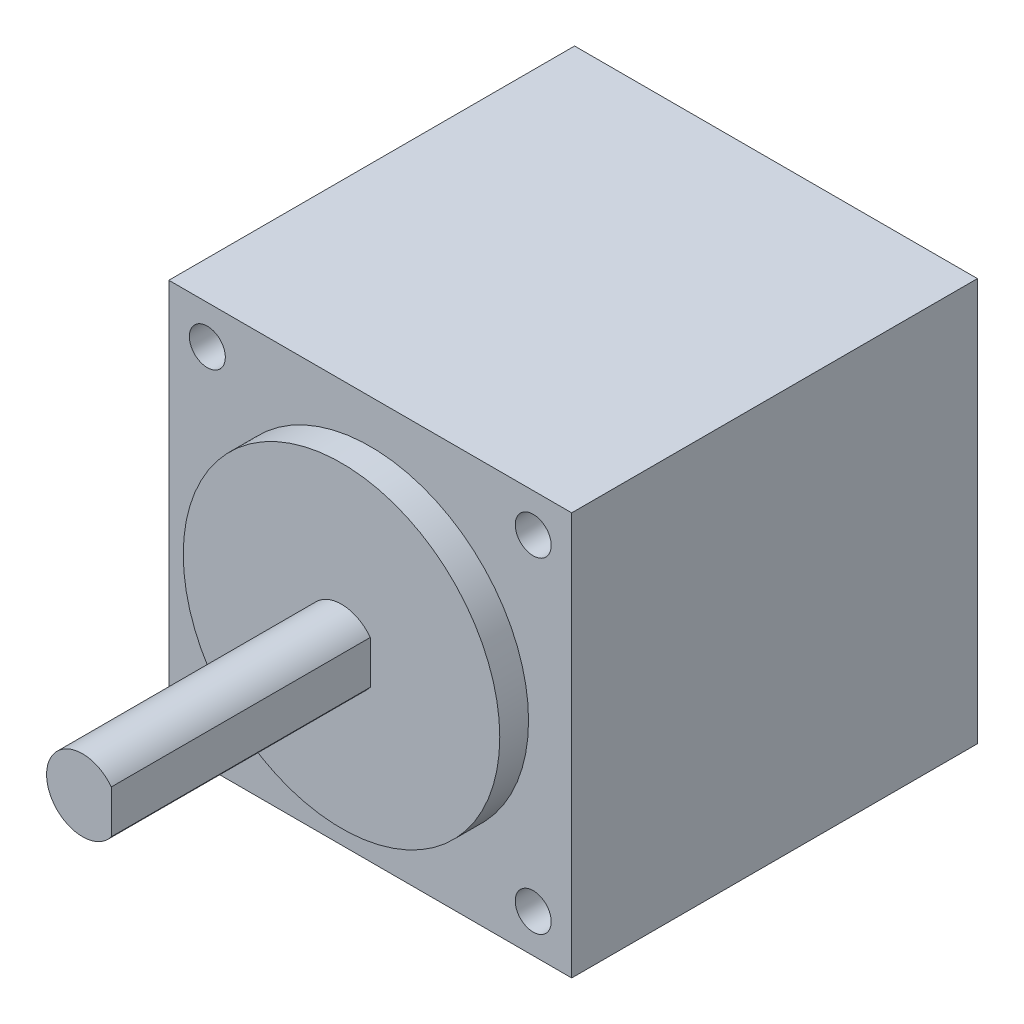
SolidWorks part; units mm, degrees
material "Plain Carbon Steel"
ref_plane "Front Plane" through (0, 0, 0) normal (0, 0, 1) x (1, 0, 0)
ref_plane "Top Plane" through (0, 0, 0) normal (0, 1, 0) x (1, 0, 0)
ref_plane "Right Plane" through (0, 0, 0) normal (1, 0, 0) x (0, 0, -1)
sketch "Sketch2" plane through (0, 0, 0) normal (0, 0, 1) x (1, 0, 0)
  line L1 (-14, -14) -> (14, -14)
  line L2 (-14, -14) -> (-14, 14)
  line L3 (-14, 14) -> (14, 14)
  line L4 (14, -14) -> (14, 14)
  line L5 (-14, -14) -> (14, 14) construction
  line L6 (-14, 14) -> (14, -14) construction
  point P0 (0, 0)
  dimension "D1" = 28
  dimension "D2" = 28
extrude "Boss-Extrude1" add sketch "Sketch2" against normal blind 28.2
sketch "Sketch3" plane through (0, 0, 0) normal (0, 0, 1) x (1, 0, 0)
  circle A0 centre (0, 0) radius 11
  dimension "D1" = 22
extrude "Boss-Extrude2" add sketch "Sketch3" along normal blind 2
sketch "Sketch4" plane through (0, 0, 0) normal (0, 0, 1) x (1, 0, 0)
  circle A0 centre (0, 0) radius 2.5
extrude "Boss-Extrude3" add sketch "Sketch4" along normal blind 20
sketch "Sketch5" plane through (0, 0, 20) normal (0, 0, 1) x (1, 0, 0)
  line L0 (2, 1.5) -> (2, -1.5)
  circle A0 centre (0, 0) radius 2.5 construction
  circle A1 centre (0, 0) radius 2.5
  point P5 (-2.5, 0)
  circle M2 centre (0, 0) radius 2.5
  dimension "D1" = 4.5
extrude "Cut-Extrude1" cut sketch "Sketch5" against normal up to surface (18 mm away) contours L0 M2 region at (2.2018, 0, 20) up to face at (2.5, 0, 2)
sketch "Sketch6" plane through (0, 0, 0) normal (0, 0, 1) x (1, 0, 0)
  line L1 (-11.325, -11.325) -> (11.325, -11.325)
  line L2 (-11.325, -11.325) -> (-11.325, 11.325)
  line L3 (-11.325, 11.325) -> (11.325, 11.325)
  line L4 (11.325, -11.325) -> (11.325, 11.325)
  line L5 (-11.325, -11.325) -> (11.325, 11.325) construction
  line L6 (-11.325, 11.325) -> (11.325, -11.325) construction
  point P0 (0, 0)
  point P7 (-11.325, 11.325)
  point P8 (11.325, 11.325)
  point P9 (11.325, -11.325)
  point P10 (-11.325, -11.325)
  dimension "D1" = 22.65
hole_wizard "Ø2.5mm Dowel Hole1" positions "Sketch7" profile "Sketch9" hole size "Ø2.5" standard "ANSI Metric"
sketch "Sketch7" plane through (0, 0, 0) normal (0, 0, 1) x (1, 0, 0)
  point P0 (-11.325, 11.325)
  point P3 (11.325, 11.325)
  point P6 (11.325, -11.325)
  point P9 (-11.325, -11.325)
sketch "Sketch9" plane through (-11.325, 11.325, 0) normal (1, 0, 0) x (0, -1, 0)
  line L0 (0, 0) -> (0, 4.7511)
  line L1 (0, 4.7511) -> (1.25, 4)
  line L2 (1.25, 4) -> (1.25, 0)
  line L5 (1.25, 0) -> (0, 0)
  line L10 (0, 4.7511) -> (-1.25, 4) construction
  line L11 (0, -6.35) -> (0, 107.95) construction
  dimension "Hole Dia." = 2.5
  dimension "Hole Depth" = 4
  dimension "Drill Angle" = 118
